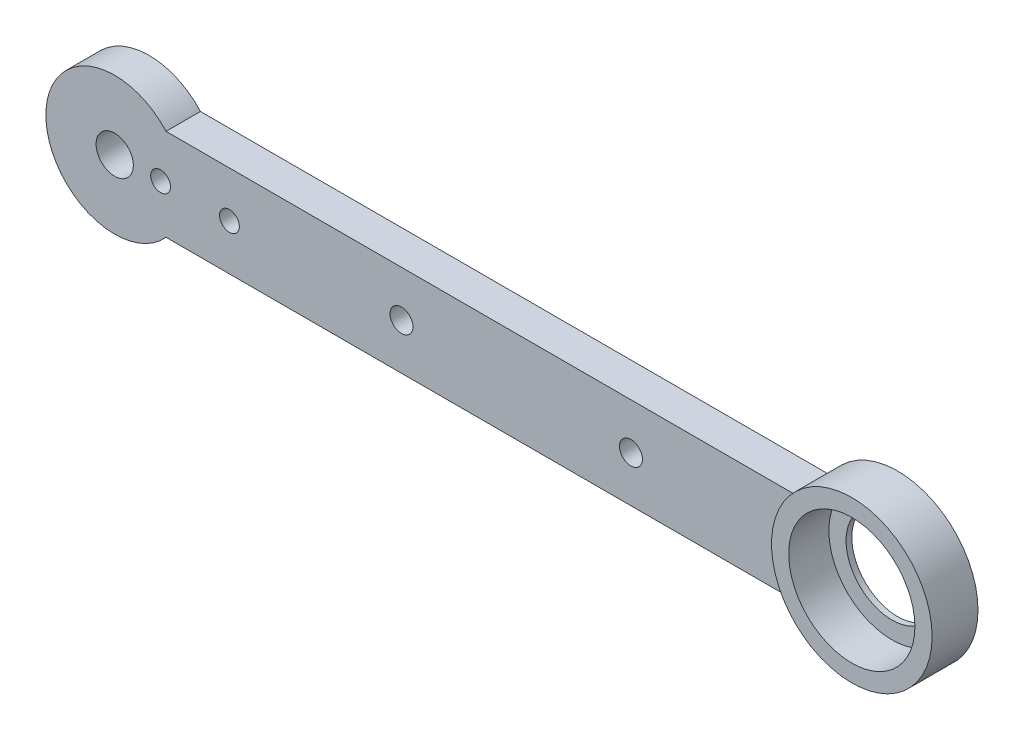
SolidWorks part; units mm, degrees
ref_plane "Front Plane" through (0, 0, 0) normal (0, 0, 1) x (1, 0, 0)
ref_plane "Top Plane" through (0, 0, 0) normal (0, 1, 0) x (1, 0, 0)
ref_plane "Right Plane" through (0, 0, 0) normal (1, 0, 0) x (0, 0, -1)
sketch "Sketch1" plane through (0, 0, 0) normal (0, 0, 1) x (1, 0, 0)
  line L0 (0, -8) -> (130, -8)
  line L1 (130, -8) -> (130, 8)
  line L2 (130, 8) -> (0, 8)
  line L3 (0, 8) -> (0, -8)
extrude "Boss-Extrude1" add sketch "Sketch1" along normal blind 6 from offset 3
sketch "Sketch2" plane through (0, 0, 0) normal (0, 0, 1) x (1, 0, 0)
  circle A0 centre (0, 0) radius 12
extrude "Boss-Extrude2" add sketch "Sketch2" along normal blind 6 from offset 3
sketch "Sketch3" plane through (0, 0, 0) normal (0, 0, 1) x (1, 0, 0)
  circle A0 centre (130, 0) radius 14
extrude "Boss-Extrude3" add sketch "Sketch3" along normal blind 6 from offset 3
sketch "Sketch4" plane through (0, 0, 0) normal (0, 0, 1) x (1, 0, 0)
  circle A0 centre (130, 0) radius 14
extrude "Boss-Extrude4" add sketch "Sketch4" along normal blind 8 from offset 2.5
sketch "Sketch5" plane through (0, 0, 0) normal (0, 0, 1) x (1, 0, 0)
  circle A0 centre (0, 0) radius 3.25
extrude "Cut-Extrude1" cut sketch "Sketch5" against normal through all and the other way through all
sketch "Sketch6" plane through (0, 0, 0) normal (0, 0, 1) x (1, 0, 0)
  circle A0 centre (8, 0) radius 1.725
  circle A1 centre (20, 0) radius 1.725
extrude "Cut-Extrude2" cut sketch "Sketch6" against normal through all and the other way through all
sketch "Sketch7" plane through (0, 0, 0) normal (0, 0, 1) x (1, 0, 0)
  circle A0 centre (8, 0) radius 2.9
extrude "Cut-Extrude3" cut sketch "Sketch7" along normal blind 2.2 from offset 3
sketch "Sketch8" plane through (0, 0, 0) normal (0, 0, 1) x (1, 0, 0)
  circle A0 centre (20, 0) radius 2.9
extrude "Cut-Extrude4" cut sketch "Sketch8" along normal blind 2.2 from offset 3
sketch "Sketch9" plane through (0, 0, 0) normal (0, 0, 1) x (1, 0, 0)
  circle A0 centre (130, 0) radius 11
extrude "Cut-Extrude5" cut sketch "Sketch9" along normal blind 7 from offset 3.5
sketch "Sketch10" plane through (0, 0, 0) normal (0, 0, 1) x (1, 0, 0)
  circle A0 centre (130, 0) radius 8
extrude "Cut-Extrude6" cut sketch "Sketch10" against normal through all and the other way through all
sketch "Sketch11" plane through (0, 0, 0) normal (0, 0, 1) x (1, 0, 0)
  circle A0 centre (50, 0) radius 2
  circle A1 centre (90, 0) radius 2
extrude "Cut-Extrude7" cut sketch "Sketch11" along normal blind 4 from offset 5
